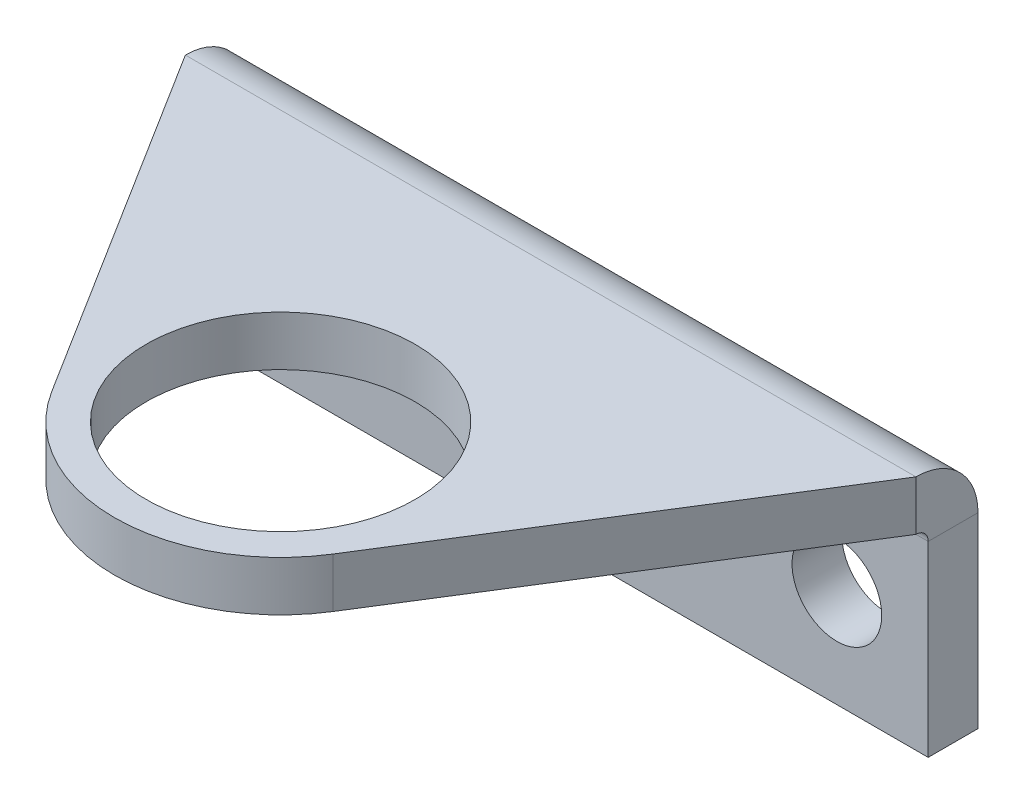
SolidWorks part; units mm, degrees
note: The reader was unsure of these and kept them because the rebuilt part matched: flange length of "Edge-Flange1".
ref_plane "Front Plane" through (0, 0, 0) normal (0, 0, 1) x (1, 0, 0)
ref_plane "Top Plane" through (0, 0, 0) normal (0, 1, 0) x (1, 0, 0)
ref_plane "Right Plane" through (0, 0, 0) normal (1, 0, 0) x (0, 0, -1)
sketch "Sketch2" plane through (0, 0, 0) normal (0, 0, 1) x (1, 0, 0)
  line L1 (0, 0) -> (44, 0)
  line L2 (0, 0) -> (0, -12)
  line L3 (0, -12) -> (44, -12)
  line L4 (44, 0) -> (44, -12)
  circle A0 centre (5.5, -6) radius 2.7
  circle A1 centre (38.5, -6) radius 2.7
  dimension "D3" = 5.4
  dimension "D4" = 5.4
  dimension "D5" = 33
  dimension "D6" = 6
  dimension "D7" = 5.5
  dimension "D8" = 6
  dimension "D1" = 44
  dimension "D2" = 12
base flange "Base-Flange1" sketch "Sketch2" thickness 3 reverse thickness direction no parameters "D1"=0.7366
edge flange "Edge-Flange1" sketch "Sketch9" flange angle 90 flange length 32.1 flange position material outside bend radius 0.7366 thickness 3 relief rectangular parameters "D6"=10
sketch "Sketch9" plane through (0, 0, 0) normal (0, 1, 0) x (-1, 0, 0)
  line L0 (-44, 0) -> (0, 0) construction
  line L1 (-44, 0) -> (0, 0)
  line L2 (-44, 0) -> (-44, 29.1)
  line L3 (-44, 29.1) -> (0, 29.1)
  line L4 (0, 29.1) -> (0, 0)
bend "EdgeBend1" bend radius 0.7366 bend angle 90 parameters "D5"=1
sketch "Sketch10" plane through (0, 0, 0) normal (0, -1, 0) x (1, 0, 0)
  line L0 (22, 29.1) -> (22, -3.858) construction
  line L1 (44, 29.1) -> (0, 29.1) construction
  line L2 (0, -3) -> (44, -3) construction
  line L3 (0, 0.7366) -> (13.5276, 22.3121)
  line L4 (44, 0.7366) -> (30.4724, 22.3121)
  line L5 (0, 0.7366) -> (-4.2853, 0.7366)
  line L6 (-4.2853, 0.7366) -> (-4.2853, 35.1086)
  line L7 (-4.2853, 35.1086) -> (48.4214, 35.1086)
  line L8 (48.4214, 35.1086) -> (48.4214, 0.7366)
  line L9 (48.4214, 0.7366) -> (44, 0.7366)
  circle A0 centre (22, 17) radius 8.1 construction
  circle A1 centre (22, 17) radius 10 construction
  arc A2 (13.5276, 22.3121) -> (30.4724, 22.3121) centre (22, 17) cw
  dimension "D1" = 20
  dimension "D2" = 16.2
  dimension "D3" = 20
extrude "Cut-Extrude1" cut sketch "Sketch10" against normal blind 10 normal cut yes
sketch "Sketch11" plane through (0, 0, 0) normal (0, -1, 0) x (1, 0, 0)
  line L0 (22, 29.1) -> (22, -5.2135) construction
  line L1 (44, 29.1) -> (0, 29.1) construction
  line L2 (0, -3) -> (44, -3) construction
  circle A0 centre (22, 17) radius 8.1
  dimension "D1" = 16.2
  dimension "D2" = 20
extrude "Cut-Extrude2" cut sketch "Sketch11" against normal blind 10 normal cut yes
sketch "Bend-Lines1" [suppressed]
sketch "Bounding-Box1" [suppressed] plane through (0, 0, 0) normal (0, 1, 0) x (1, 0, 0)
sheet metal parameters "Sheet-Metal1" thickness 3 parameters "D1"=0.7366
flat pattern "Flat-Pattern1" [suppressed]
sketch "Bend-Lines2" plane through (0, 0, 0) normal (0, 1, 0) x (1, 0, 0)
sketch3d "Bounding-Box2" [suppressed]
  line L0 (0, -12, 0) -> (-44, -12, 0) construction
  line L1 (0, 0, 0) -> (-44, 0, 0) construction
  line L2 (0, -12, 0) -> (0, 0, 0) construction
  line L3 (-44, -12, 0) -> (-44, 0, 0) construction
sheet metal parameters "Sheet-Metal2" thickness 3 parameters "D1"=0.7366
flat pattern "Flat-Pattern1"
sketch "Bend-Lines2" plane through (0, 0, 0) normal (0, 0, 1) x (1, 0, 0)
  line L0 (44, -0.1581) -> (0, -0.1581) construction
  line L1 (44, -0.1581) -> (0, -0.1581) construction
sketch3d "Bounding-Box2" [suppressed]
  line L0 (0, -12, 0) -> (44, -12, 0) construction
  line L1 (0, 28.7838, 0) -> (44, 28.7838, 0) construction
  line L2 (0, -12, 0) -> (0, 28.7838, 0) construction
  line L3 (44, -12, 0) -> (44, 28.7838, 0) construction
bend of the flat pattern "Flatten-<EdgeBend1>1"
sheet metal parameters "Sheet-Metal3" thickness 3 parameters "D1"=0.7366
flat pattern "Flat-Pattern1"
sketch "Bend-Lines2" plane through (0, 0, 0) normal (0, 0, 1) x (1, 0, 0)
  line L0 (44, -0.1581) -> (0, -0.1581) construction
  line L1 (44, -0.1581) -> (0, -0.1581) construction
sketch3d "Bounding-Box2" [suppressed]
  line L0 (0, 26.6838, 0) -> (44, 26.6838, 0) construction
  line L1 (0, -12, 0) -> (44, -12, 0) construction
  line L2 (0, 26.6838, 0) -> (0, -12, 0) construction
  line L3 (44, 26.6838, 0) -> (44, -12, 0) construction
bend of the flat pattern "Flatten-<EdgeBend1>1"
sheet metal parameters "Sheet-Metal4" thickness 3 parameters "D1"=0.7366
flat pattern "Flat-Pattern1"
sketch "Bend-Lines2" plane through (0, 0, 0) normal (0, 0, 1) x (1, 0, 0)
  line L0 (44, -0.1581) -> (0, -0.1581) construction
  line L1 (44, -0.1581) -> (0, -0.1581) construction
sketch3d "Bounding-Box2" [suppressed]
  line L0 (0, 26.6838, 0) -> (44, 26.6838, 0) construction
  line L1 (0, -12, 0) -> (44, -12, 0) construction
  line L2 (0, 26.6838, 0) -> (0, -12, 0) construction
  line L3 (44, 26.6838, 0) -> (44, -12, 0) construction
bend of the flat pattern "Flatten-<EdgeBend1>1"
